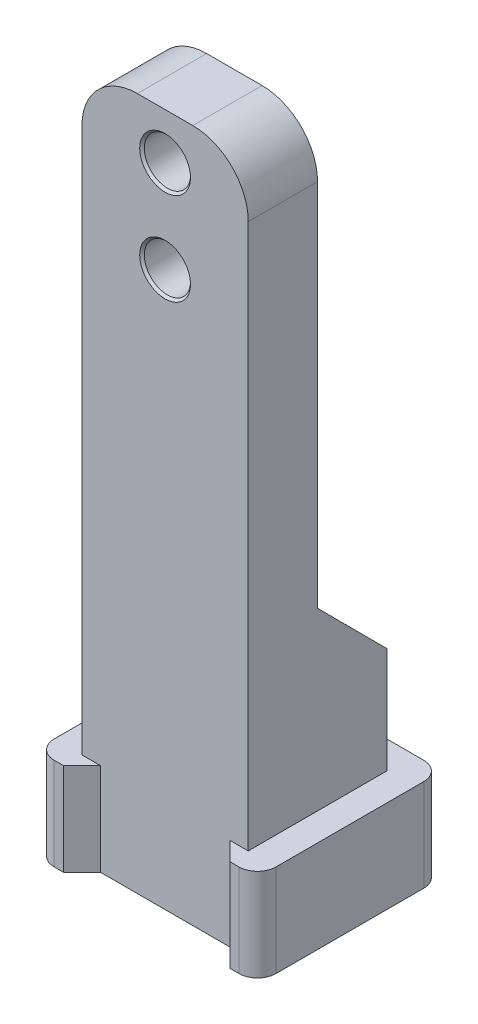
SolidWorks part; units mm, degrees
ref_plane "Front Plane" through (0, 0, 0) normal (0, 0, 1) x (1, 0, 0)
ref_plane "Top Plane" through (0, 0, 0) normal (0, 1, 0) x (1, 0, 0)
ref_plane "Right Plane" through (0, 0, 0) normal (1, 0, 0) x (0, 0, -1)
sketch "Sketch1" plane through (0, 0, 0) normal (0, 1, 0) x (1, 0, 0)
  line L1 (0, 0) -> (18, 0)
  line L2 (0, 0) -> (0, 15)
  line L3 (0, 15) -> (18, 15)
  line L4 (18, 0) -> (18, 15)
extrude "Boss-Extrude1" add sketch "Sketch1" along normal blind 75
sketch "Sketch2" plane through (0, 0, 0) normal (0, -1, 0) x (1, 0, 0)
  line L0 (9, 0) -> (9, -6)
  line L1 (0, 0) -> (18, 0) construction
  line L3 (9, -6) -> (14, -6)
  line L4 (9, -6) -> (4, -6)
  circle A0 centre (14, -6) radius 2.5
  circle A1 centre (4, -6) radius 2.5
extrude "Cut-Extrude1" cut sketch "Sketch2" against normal blind 12 contours A1 | A0 region at (14, 0, -3.5707) region at (1.5707, 0, -6)
sketch "Sketch3" plane through (18, 0, 0) normal (1, 0, 0) x (0, 0, -1)
  line L6 (7.5, 75) -> (7.5, 29)
  line L7 (0, 75) -> (15, 75) construction
  line L8 (7.5, 29) -> (15, 21.4721)
  line L9 (15, 75) -> (15, 0) construction
  line L10 (7.5, 75) -> (15, 75)
  line L11 (15, 75) -> (15, 21.4721)
extrude "Cut-Extrude2" cut sketch "Sketch3" against normal blind 48
sketch "Sketch4" plane through (0, 0, 0) normal (0, 0, 1) x (1, 0, 0)
  line L0 (9, 75) -> (9, 70)
  line L1 (0, 75) -> (18, 75) construction
  line L2 (9, 70) -> (9, 60)
  circle A0 centre (9, 70) radius 2.5
  circle A1 centre (9, 60) radius 2.5
  dimension "D1" = 10
extrude "Cut-Extrude3" cut sketch "Sketch4" against normal blind 48 contours L2 A0 L0 | L0 A0 L2 | A1 region at (10.061, 70, 0) region at (10.7178, 61.7178, 0) region at (7.939, 70, 0)
fillet "Fillet1" radius 6 2 edges at (0, 75, -3.75) (18, 75, -3.75)
sketch "Sketch5" plane through (0, 0, 0) normal (0, -1, 0) x (1, 0, 0)
  line L0 (0, 0) -> (0, 2)
  line L1 (0, 2) -> (-3, 2)
  line L2 (-3, 2) -> (-3, -18)
  line L3 (18, 0) -> (18, 2)
  line L4 (18, 2) -> (21, 2)
  line L5 (21, 2) -> (21, -18)
  line L6 (21, -18) -> (-3, -18)
  line L7 (0, 0) -> (0, -15)
  line L8 (0, -15) -> (18, -15)
  line L9 (18, -15) -> (18, 0)
extrude "Boss-Extrude2" add sketch "Sketch5" against normal blind 10
chamfer "Chamfer3" distance 2 angle 45 2 edges at (0, 5, 0) (18, 5, 0)
fillet "Fillet2" radius 2 4 edges at (21, 5, -18) (-3, 5, -18) (-3, 5, 2) (21, 5, 2)
chamfer "Chamfer4" distance 0.25 angle 45 4 edges at (11.5, 70, 0) (11.5, 60, 0) (14, 0, -8.5) (4, 0, -8.5)
